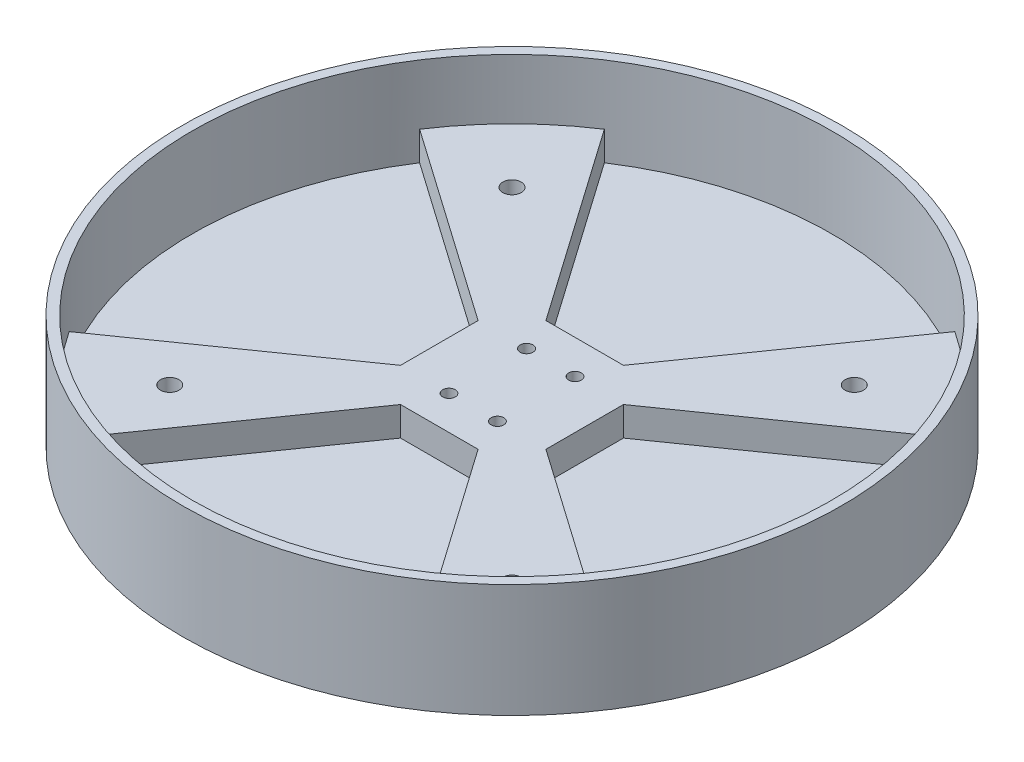
SolidWorks part; units mm, degrees
ref_plane "Front Plane" through (0, 0, 0) normal (0, 0, 1) x (1, 0, 0)
ref_plane "Top Plane" through (0, 0, 0) normal (0, 1, 0) x (1, 0, 0)
ref_plane "Right Plane" through (0, 0, 0) normal (1, 0, 0) x (0, 0, -1)
sketch "Sketch1" plane through (0, 0, 0) normal (0, 1, 0) x (1, 0, 0)
  circle A0 centre (0, 0) radius 83.82
  circle A1 centre (0, 0) radius 86.36
  dimension "D1" = 167.64
  dimension "D2" = 2.54
extrude "Boss-Extrude1" add sketch "Sketch1" along normal blind 28.45
extrude "Boss-Extrude2" add sketch "Sketch1<2>" against normal blind 1.27 contours A0 | A1 A0
sketch "Sketch1<2>" plane through (0, 0, 0) normal (0, 1, 0) x (1, 0, 0) same geometry as "Sketch1"
sketch "Sketch2" plane through (0, 0, 0) normal (0, 1, 0) x (1, 0, 0)
  line L1 (-44.845, -44.845) -> (-15.24, -44.845) construction
  line L2 (-44.845, -44.845) -> (-44.845, -42.432) construction
  line L3 (-44.845, 44.845) -> (44.845, 44.845) construction
  line L4 (44.845, -44.845) -> (44.845, 44.845) construction
  line L5 (-44.845, -44.845) -> (-43.1388, -43.1388) construction
  line L6 (-44.845, 44.845) -> (-43.1388, 43.1388) construction
  line L7 (-57.15, -57.15) -> (-15.24, -57.15)
  line L8 (-57.15, -57.15) -> (-57.15, 57.15) construction
  line L9 (-57.15, 57.15) -> (57.15, 57.15) construction
  line L10 (57.15, -57.15) -> (57.15, 57.15) construction
  line L11 (-57.15, -57.15) -> (-43.1388, -43.1388) construction
  line L12 (-57.15, 57.15) -> (-43.1388, 43.1388) construction
  line L20 (-15.24, -17.78) -> (-15.24, -57.15) construction
  line L22 (15.24, -17.78) -> (15.24, -57.15) construction
  line L23 (43.1388, -43.1388) -> (57.15, -57.15) construction
  line L24 (43.1388, -43.1388) -> (44.845, -44.845) construction
  line L25 (15.24, -57.15) -> (57.15, -57.15) construction
  line L26 (15.24, -44.845) -> (44.845, -44.845) construction
  line L27 (-15.24, -17.78) -> (15.24, -17.78) construction
  line L28 (-44.845, 42.432) -> (-44.845, 44.845) construction
  line L29 (43.1388, 43.1388) -> (44.845, 44.845) construction
  line L30 (43.1388, 43.1388) -> (57.15, 57.15) construction
  circle A0 centre (44.845, 44.845) radius 2.413
  circle A1 centre (44.845, -44.845) radius 2.413
  circle A2 centre (-44.845, -44.845) radius 2.413
  circle A3 centre (-44.845, 44.845) radius 2.413
  circle A4 centre (0, 0) radius 83.82
  point P0 (0, 0)
  point P6 (0, 0)
  point P15 (0, 0)
  dimension "D3" = 4.826
  dimension "D4" = 4.826
  dimension "D5" = 4.826
  dimension "D6" = 4.826
  dimension "D1" = 89.69
  dimension "D2" = 114.3
extrude "Boss-Extrude3" add sketch "Sketch2" along normal blind 12.7 contours A3 A2 A1 A0 region at (0, 0, 0)
sketch "Sketch3" plane through (0, 12.7, 0) normal (0, 1, 0) x (1, 0, 0)
  line L11 (-6.35, -10.16) -> (6.35, -10.16) construction
  line L12 (-6.35, -10.16) -> (-6.35, 10.16) construction
  line L13 (-6.35, 10.16) -> (6.35, 10.16) construction
  line L14 (6.35, -10.16) -> (6.35, 10.16) construction
  line L15 (-6.35, -10.16) -> (6.35, 10.16) construction
  line L16 (-6.35, 10.16) -> (6.35, -10.16) construction
  circle A0 centre (6.35, 10.16) radius 1.651
  circle A1 centre (6.35, -10.16) radius 1.651
  circle A2 centre (-6.35, -10.16) radius 1.651
  circle A3 centre (-6.35, 10.16) radius 1.6813
  circle A4 centre (0, 0) radius 83.82 construction
  circle A5 centre (0, 0) radius 83.82 construction
  point P4 (0, 0)
  dimension "D3" = 3.302
  dimension "D4" = 3.302
  dimension "D5" = 3.302
  dimension "D6" = 3.3626
  dimension "D1" = 12.7
  dimension "D2" = 20.32
extrude "Cut-Extrude1" cut sketch "Sketch3" against normal blind 2.54
sketch "Sketch4" plane through (0, 12.7, 0) normal (0, 1, 0) x (1, 0, 0)
  line L0 (-70.1218, 45.9209) -> (-19.05, 10.16)
  line L1 (-70.1218, -45.9209) -> (-19.05, -10.16)
  line L2 (-19.05, -10.16) -> (-19.05, 10.16)
  line L3 (-10.16, 19.05) -> (10.16, 19.05)
  line L4 (45.9209, 70.1218) -> (10.16, 19.05)
  line L5 (-45.9209, 70.1218) -> (-10.16, 19.05)
  line L6 (19.05, 10.16) -> (19.05, -10.16)
  line L7 (70.1218, -45.9209) -> (19.05, -10.16)
  line L8 (70.1218, 45.9209) -> (19.05, 10.16)
  line L9 (10.16, -19.05) -> (-10.16, -19.05)
  line L10 (-45.9209, -70.1218) -> (-10.16, -19.05)
  line L11 (45.9209, -70.1218) -> (10.16, -19.05)
  arc A0 (-70.1218, 45.9209) -> (-70.1218, -45.9209) centre (0, 0) ccw
  circle A1 centre (0, 0) radius 83.82 construction
  circle A2 centre (0, 0) radius 83.82 construction
  circle A3 centre (-6.35, -10.16) radius 1.651 construction
  circle A4 centre (6.35, -10.16) radius 1.651 construction
  circle A5 centre (6.35, 10.16) radius 1.651 construction
  circle A6 centre (-6.35, 10.16) radius 1.6813 construction
  circle A7 centre (-6.35, -10.16) radius 1.651 construction
  circle A8 centre (6.35, -10.16) radius 1.651 construction
  circle A9 centre (6.35, 10.16) radius 1.651 construction
  circle A10 centre (-6.35, 10.16) radius 1.6813 construction
  arc A11 (45.9209, 70.1218) -> (-45.9209, 70.1218) centre (0, 0) ccw
  arc A12 (70.1218, -45.9209) -> (70.1218, 45.9209) centre (0, 0) ccw
  arc A13 (-45.9209, -70.1218) -> (45.9209, -70.1218) centre (0, 0) ccw
  point P6 (-67.5743, 49.5935)
  point P23 (-67.5743, -49.5935)
  point P37 (0, 0)
  dimension "D1" = 12.7
  dimension "D3" = 125
  dimension "D4" = 125
  dimension "D2" = 4
extrude "Cut-Extrude2" cut sketch "Sketch4" against normal blind 7.62
